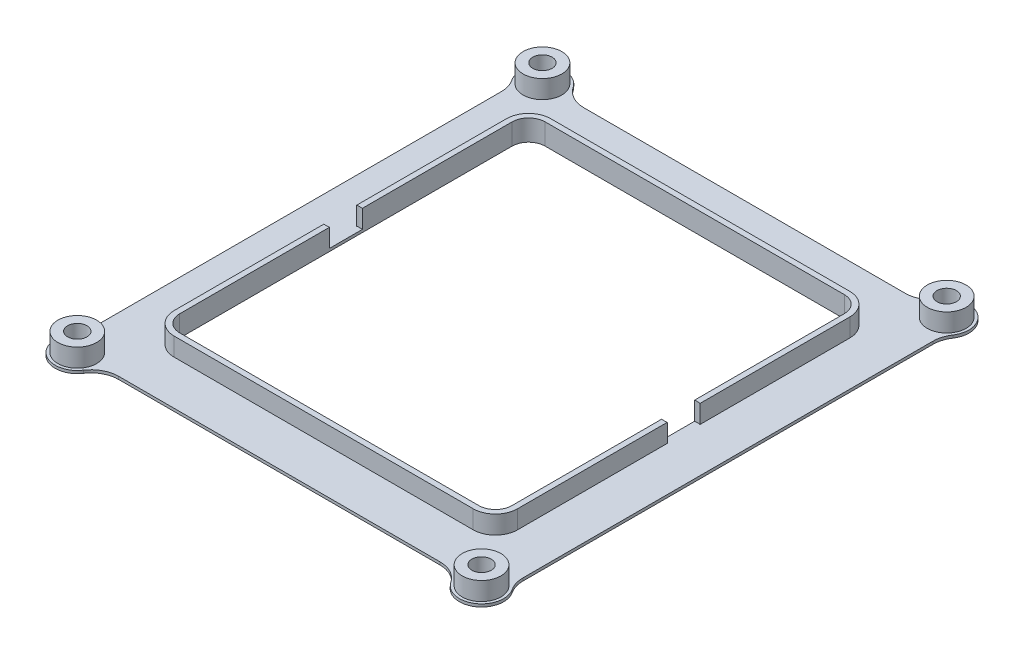
SolidWorks part; units mm, degrees
material "6061-T6 (SS)"
ref_plane "Front Plane" through (0, 0, 0) normal (0, 0, 1) x (1, 0, 0)
ref_plane "Top Plane" through (0, 0, 0) normal (0, 1, 0) x (1, 0, 0)
ref_plane "Right Plane" through (0, 0, 0) normal (1, 0, 0) x (0, 0, -1)
sketch "Sketch1" plane through (0, 0, 0) normal (0, 1, 0) x (1, 0, 0)
  line L0 (-33, 42) -> (33, 42)
  line L1 (-36.5, -42) -> (36.5, -42) construction
  line L2 (-36.5, -42) -> (-36.5, 42) construction
  line L3 (-36.5, 42) -> (36.5, 42) construction
  line L4 (36.5, -42) -> (36.5, 42) construction
  line L5 (-36.5, -42) -> (36.5, 42) construction
  line L6 (-36.5, 42) -> (36.5, -42) construction
  line L7 (36.5, 38.5) -> (36.5, -38.5)
  line L8 (33, -42) -> (-33, -42)
  line L9 (-36.5, -38.5) -> (-36.5, 38.5)
  line L11 (35.5, -41) -> (-35.5, -41)
  line L12 (35.5, -41) -> (35.5, 41)
  line L13 (35.5, 41) -> (-35.5, 41)
  line L14 (-35.5, -41) -> (-35.5, 41)
  line L15 (35.5, -41) -> (-35.5, 41) construction
  line L16 (35.5, 41) -> (-35.5, -41) construction
  circle A0 centre (-36.5, 42) radius 1.75
  circle A1 centre (36.5, 42) radius 1.75
  circle A2 centre (36.5, -42) radius 1.75
  circle A3 centre (-36.5, -42) radius 1.75
  circle A4 centre (-36.5, -42) radius 3.5
  circle A5 centre (-36.5, 42) radius 3.5
  circle A6 centre (36.5, 42) radius 3.5
  circle A7 centre (36.5, -42) radius 3.5
  point P0 (0, 0)
  point P22 (0, 0)
  dimension "D3" = 3.5
  dimension "D4" = 7
  dimension "D1" = 84
  dimension "D2" = 73
  dimension "D5" = 1
  dimension "D6" = 1
extrude "FrameAndBoltHoles" add sketch "Sketch1" along normal blind 3.8 contours A6 L0 A5 L13 | A5 L14 A0 L13 | L14 A5 L13 A0 | A5 L9 A4 L14 | A4 L11 A3 L14 | L11 A4 L14 A3 | A7 L11 A4 L8 | L12 A7 L11 A2 | A7 L12 A2 L11 | A7 L7 A6 L12 | L13 A6 L12 A1 | A6 L13 A1 L12 region at (-33.1346, 0, -41.509) region at (0, 0, -41.4996) region at (36.5, 0, -45.401) region at (-35.9997, 0, 0) region at (-34.5625, 0, -40.0625) region at (34.5625, 0, -40.0625) region at (-36.009, 0, 38.6346) region at (35.9997, 0, 0) region at (0, 0, 41.4996) region at (-34.5625, 0, 40.0625) region at (38.9049, 0, 39.5951) region at (34.5625, 0, 40.0625)
sketch "Sketch2" plane through (0, 0, 0) normal (0, 1, 0) x (1, 0, 0)
  line L0 (-35.5, -38.6459) -> (-35.5, 38.6459) construction
  line L1 (33.1459, 41) -> (-33.1459, 41) construction
  line L2 (-35.5, -38.6459) -> (-35.5, 38.6459)
  line L3 (33.1459, 41) -> (-33.1459, 41)
  circle A0 centre (-31, 36.5) radius 4.5
  arc A1 (-35.5, 38.6459) -> (-33.1459, 41) centre (-36.5, 42) ccw construction
  arc A2 (-35.5, 38.6459) -> (-33.1459, 41) centre (-36.5, 42) ccw
  dimension "D1" = 9
extrude "InsideFillet" add sketch "Sketch2" along normal up to surface (3.8 mm away) contours A2 L2 A0 L3 region at (-35.2954, 0, -38.216) up to face at (0, 3.8, 0)
mirror "MirrorFillet" about plane through (0, 0, 0) normal (1, 0, 0) of "InsideFillet"
mirror "MirrorFillet2" about plane through (0, 0, 0) normal (0, 0, 1) of "MirrorFillet"
sketch "Sketch3" plane through (0, 0, 0) normal (0, 1, 0) x (1, 0, 0)
  line L0 (-27, 41) -> (-27, 30)
  line L1 (33.1459, 41) -> (-33.1459, 41) construction
  line L2 (-27, 30) -> (-35.5, 30)
  line L3 (-35.5, -36.5) -> (-35.5, 36.5) construction
  line L4 (-35.5, -36.5) -> (-35.5, 36.5)
  line L5 (33.1459, 41) -> (-31, 41)
  line L6 (-27, 33) -> (-19, 41)
  line L7 (33.1459, 41) -> (-33.1459, 41) construction
  line L8 (-30, 30) -> (-35.5, 24.5)
  line L9 (-27, 30) -> (27, 30) construction
  line L11 (-27, 30) -> (-27, -30) construction
  line L13 (27, 30) -> (35.5, 30) construction
  line L14 (35.5, -36.5) -> (35.5, 36.5) construction
  line L15 (-27, -30) -> (-27, -41) construction
  line L16 (33.1459, -41) -> (-33.1459, -41) construction
  circle A0 centre (-27, 30) radius 4
  circle A1 centre (-27, 30) radius 3
  arc A3 (-31, 41) -> (-35.5, 36.5) centre (-31, 36.5) ccw
  point P8 (-27, 34)
  point P9 (-31, 30)
  point P16 (27, 30)
  dimension "D1" = 54
  dimension "D3" = 8
  dimension "D4" = 6
  dimension "D2" = 60
  dimension "D5" = 45
  dimension "D6" = 45
extrude "WireTrough" add sketch "Sketch3" along normal blind 0.5 contours A0 L6 L5 L0 | L5 A3 L4 L2 A0 L0 | A0 L2 L4 L8 | L6 A0 L0 | A1 L0 A0 L2 | L2 A0 L8 region at (-29.2433, 0, -32.2433) region at (-26.6957, 0, -33.6435) region at (-31.4847, 0, -35.8688) region at (-24.2985, 0, -38.4024) region at (-30.6435, 0, -29.6957) region at (-33.7624, 0, -28.1182)
sketch "Sketch4" plane through (0, 0.5, 0) normal (0, 1, 0) x (1, 0, 0)
  line L0 (-27, 33) -> (-19, 41) construction
  line L1 (-30, 30) -> (-35.5, 24.5) construction
  line L2 (-27, 33) -> (-19, 41)
  line L3 (-30, 30) -> (-35.5, 24.5)
  line L4 (0, 41) -> (0, 0) construction
  line L5 (0, 0) -> (-35.5, 0) construction
  line L6 (-35.5, -36.5) -> (-35.5, 24.5) construction
  line L7 (33.1459, 41) -> (-19, 41) construction
  line L8 (-27, 33) -> (0, 33)
  line L9 (0, 33) -> (0, 34)
  line L10 (0, 34) -> (-27, 34)
  line L11 (-30, 30) -> (-30, 0)
  line L12 (-31, 30) -> (-31, 0)
  line L13 (-31, 0) -> (-30, 0)
  line L14 (-27, 33) -> (-30, 30)
  circle A1 centre (-27, 30) radius 4
  arc A3 (-27, 33) -> (-30, 30) centre (-27, 30) ccw construction
  arc A4 (-27, 33) -> (-30, 30) centre (-27, 30) ccw
  arc A5 (-27, 33) -> (-30, 30) centre (-27, 30) ccw
  line M3 (-35.5, 24.5) -> (-30, 30)
  arc M4 (-30, 30) -> (-27, 33) centre (-27, 30) cw
  line M5 (-27, 33) -> (-19, 41)
  dimension "D1" = 8
extrude "WireInsideWall" add sketch "Sketch4" along normal up to surface (3.3 mm away) contours A1 L3 M5 M4 | A1 L8 L9 L10 L2 | L8 A1 M5 | A1 L11 M3 | A1 L3 L12 L13 L11 | A1 L2 L10 | A1 L12 L3 region at (-29.1604, 0.5, -32.1604) region at (-25.7456, 0.5, -33.3224) region at (-26.2882, 0.5, -33.9689) region at (-12.5815, 0.5, -33.5062) region at (-30.3224, 0.5, -28.7456) region at (-30.5056, 0.5, -14.0809) region at (-30.9689, 0.5, -29.2882) up to face at (0, 3.8, 0)
mirror "WireSpaceMirror" about plane through (0, 0, 0) normal (1, 0, 0) of "WireInsideWall", "WireTrough"
mirror "WireSpaceMirror2" about plane through (0, 0, 0) normal (0, 0, 1) of "WireSpaceMirror"
ref_plane "Plane1" through (0, 1.05, 0) normal (0, 1, 0) x (1, 0, 0)
sketch "Sketch6" plane through (0, 1.05, 0) normal (0, 1, 0) x (1, 0, 0)
  line L0 (-27, 30) -> (-27, 41) construction
  line L1 (-19, 41) -> (-31, 41) construction
  line L2 (-27, 30) -> (-35.5, 30) construction
  line L3 (-37.5, 30) -> (-37.5, 0)
  line L4 (-35.5, 24.5) -> (-35.5, 36.5) construction
  line L5 (0, 41) -> (0, 0) construction
  line L6 (33.1459, 41) -> (-33.1459, 41) construction
  line L7 (0, 0) -> (-35.5, 0) construction
  line L9 (-35.5, -36.5) -> (-35.5, 36.5) construction
  line L10 (-27, 40.5) -> (0, 40.5)
  line L11 (-27, 36) -> (-27, 37) construction
  line L12 (0, 39.5) -> (-27, 39.5)
  line L13 (-27, 39.5) -> (-27, 37) construction
  line L14 (-27, 37) -> (0, 37)
  line L15 (-27, 39.5) -> (-27, 40.5) construction
  line L16 (0, 36) -> (-27, 36)
  line L17 (-27, 40.5) -> (-27, 41) construction
  line L18 (-27, 35.5) -> (-27, 36) construction
  line L19 (-36.5, 0) -> (-36.5, 30)
  line L20 (-34, 30) -> (-34, 0)
  line L21 (-33, 30) -> (-33, 0)
  arc A0 (-27, 40.5) -> (-37.5, 30) centre (-27, 30) ccw
  arc A1 (-27, 39.5) -> (-36.5, 30) centre (-27, 30) ccw
  arc A2 (-27, 37) -> (-34, 30) centre (-27, 30) ccw
  arc A3 (-27, 36) -> (-33, 30) centre (-27, 30) ccw
  dimension "D1" = 0.5
  dimension "D2" = 1
  dimension "D3" = 1
  dimension "D4" = 0.5
sketch "Sketch7" plane through (0, 0.5, 0) normal (0, -1, 0) x (1, 0, 0)
  line L0 (19, -41) -> (-19, -41) construction
  line L1 (-35.5, 41) -> (35.5, 41)
  line L2 (-35.5, 41) -> (-35.5, -41)
  line L3 (-35.5, -41) -> (35.5, -41)
  line L4 (35.5, 41) -> (35.5, -41)
  line L5 (-35.5, 41) -> (35.5, -41) construction
  line L6 (-35.5, -41) -> (35.5, 41) construction
  line L7 (-30, 33) -> (30, 33)
  line L8 (-30, 33) -> (-30, -33)
  line L9 (-30, -33) -> (30, -33)
  line L10 (30, 33) -> (30, -33)
  line L11 (-30, 33) -> (30, -33) construction
  line L12 (-30, -33) -> (30, 33) construction
  line L13 (35.5, 24.5) -> (35.5, -24.5) construction
  line L14 (-27, -33) -> (27, -33) construction
  line L15 (30, -30) -> (30, 30) construction
  circle A0 centre (36.5, -42) radius 1.75
  circle A1 centre (-36.5, -42) radius 1.75
  circle A2 centre (-36.5, 42) radius 1.75
  circle A3 centre (36.5, 42) radius 1.75
  circle A5 centre (36.5, 42) radius 1.75 construction
  circle A6 centre (-36.5, 42) radius 1.75 construction
  circle A7 centre (-36.5, -42) radius 1.75 construction
  circle A8 centre (36.5, -42) radius 1.75 construction
  point P0 (0, 0)
  point P6 (0, 0)
  line M13 (27, -33) -> (-27, -33)
  line M14 (-27, -33) -> (-26, -34)
  line M15 (-26, -34) -> (26, -34)
  line M16 (26, -34) -> (27, -33)
extrude "InnerRing" add sketch "Sketch7" along normal up to surface (0.5 mm away) contours M16 M13 M14 M15 | A3 L1 A2 L2 A1 L3 A0 L4 L7 L10 L9 L8 M16 M15 M14 region at (0, 0.5, 39.9153) region at (0, 0.5, -33.4969) up to face at (0, 0, 0)
sketch "Sketch8" plane through (0, 3.8, 0) normal (0, 1, 0) x (1, 0, 0)
  line L0 (-27, 34) -> (27, 34) construction
  line L1 (31, -34) -> (-31, -34)
  line L2 (31, -34) -> (31, 34)
  line L3 (31, 34) -> (-31, 34)
  line L4 (-31, -34) -> (-31, 34)
  line L5 (31, -34) -> (-31, 34) construction
  line L6 (31, 34) -> (-31, -34) construction
  line L7 (50, -50) -> (-50, -50)
  line L8 (50, -50) -> (50, 50)
  line L9 (50, 50) -> (-50, 50)
  line L10 (-50, -50) -> (-50, 50)
  line L11 (50, -50) -> (-50, 50) construction
  line L12 (50, 50) -> (-50, -50) construction
  line L13 (-31, 30) -> (-31, -30) construction
  circle A0 centre (-36.5, 42) radius 3.5
  circle A1 centre (36.5, 42) radius 3.5
  circle A2 centre (36.5, -42) radius 3.5
  circle A3 centre (-36.5, -42) radius 3.5
  point P16 (0, 0)
  point P22 (0, 0)
  dimension "D1" = 100
  dimension "D2" = 100
extrude "RemoveOuterRing" cut sketch "Sketch8" against normal up to surface (3.3 mm away) up to face at (0, 0.5, 0)
sketch "Sketch9" plane through (0, 0, 0) normal (0, -1, 0) x (1, 0, 0)
  line L0 (0, 0) -> (0, -33) construction
  line L1 (-27, -33) -> (27, -33) construction
  line L2 (0, -33) -> (0, -46)
  line L5 (-40.5, 0) -> (-31, 0)
  line L6 (-31, 0) -> (0, 0) construction
  line L7 (-31, -30) -> (-31, 30) construction
  line L8 (-36.5, -46) -> (0, -46)
  line L9 (-40.5, -42) -> (-40.5, 0)
  circle A0 centre (-36.5, -42) radius 4
  circle A1 centre (-36.5, -42) radius 3.5 construction
  line M24 (-36.5, 38.5) -> (-36.5, -38.5)
  arc M25 (-36.5, -38.5) -> (-33, -42) centre (-36.5, -42) ccw
  line M26 (-33, -42) -> (33, -42)
  dimension "D1" = 0.5
extrude "Boss-Extrude2" add sketch "Sketch9" against normal up to surface (0.5 mm away) contours A0 M26 M25 M24 region at (-33.7516, 0, -44.7484) up to face at (0, 0.5, 0)
mirror "Mirror1" about plane through (0, 0, 0) normal (1, 0, 0) of "Boss-Extrude2"
mirror "Mirror2" about plane through (0, 0, 0) normal (0, 0, 1) of "Mirror1"
sketch "Sketch10" plane through (0, 0.5, 0) normal (0, 1, 0) x (1, 0, 0)
  line L0 (36.5, 38) -> (36.5, -38) construction
  line L1 (36.5, -38.8775) -> (39, -38.8775)
  line L2 (36.5, -38.8775) -> (36.5, 39.5505)
  line L3 (36.5, 39.5505) -> (39, 39.5505)
  line L4 (39, -38.8775) -> (39, 39.5505)
  line L5 (-36.5, -39.5505) -> (-39, -39.5505)
  line L6 (-36.5, -39.5505) -> (-36.5, 39.5505)
  line L7 (-36.5, 39.5505) -> (-39, 39.5505)
  line L8 (-39, -39.5505) -> (-39, 39.5505)
  line L11 (-36.5, -38) -> (-36.5, 38) construction
  circle A1 centre (36.5, 42) radius 3.5 construction
  circle A3 centre (-36.5, 42) radius 3.5 construction
  arc A4 (32.5, -42) -> (36.5, -38) centre (36.5, -42) ccw construction
  circle A5 centre (-36.5, -42) radius 3.5 construction
  dimension "D1" = 2.5
  dimension "D2" = 2.5
extrude "Boss-Extrude3" add sketch "Sketch10" against normal up to surface (0.5 mm away) up to face at (0, 0, 0)
fillet "Fillet1" radius 5 8 edges at (-32.5, 0.25, -42) (32.5, 0.25, -42) (39, 0.25, -38.8775) (39, 0.25, 38.8775) (32.5, 0.25, 42) (-32.5, 0.25, 42) (-39, 0.25, 38.8775) (-39, 0.25, -38.8775)
sketch "Sketch11" plane through (0, 3.8, 0) normal (0, 1, 0) x (1, 0, 0)
  line L2 (0, 0) -> (0, -65.5856) construction
  line L3 (31, 0) -> (30, 0) construction
  line L4 (31, 30) -> (31, -30) construction
  line L5 (30, 30) -> (30, -30) construction
  circle A0 centre (30.5, 0) radius 3
  circle A1 centre (-30.5, 0) radius 3
  point P3 (30.438, 0)
  point P7 (30.5, 0)
  dimension "D1" = 6
extrude "Cut-Extrude1" cut sketch "Sketch11" against normal up to surface (3.3 mm away) up to face at (-36.5, 0.5, -38.5)
